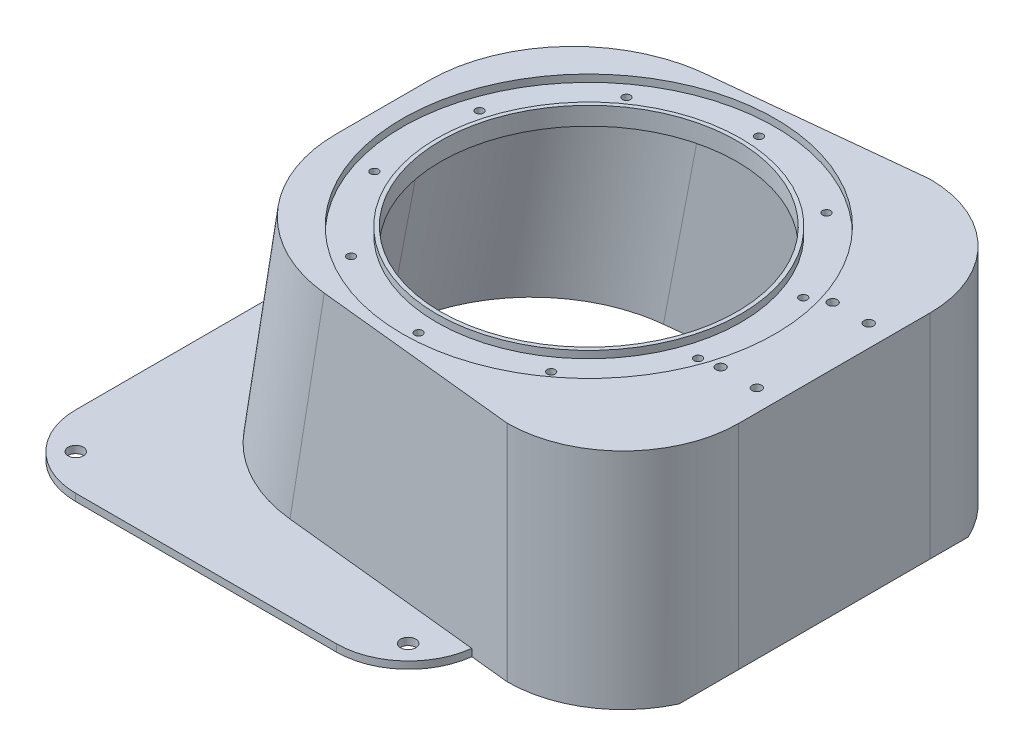
SolidWorks part; units mm, degrees
ref_plane "정면" through (0, 0, 0) normal (0, 0, 1) x (1, 0, 0)
ref_plane "윗면" through (0, 0, 0) normal (0, 1, 0) x (1, 0, 0)
ref_plane "우측면" through (0, 0, 0) normal (1, 0, 0) x (0, 0, -1)
sketch "스케치1" plane through (0, 0, 0) normal (0, 1, 0) x (1, 0, 0)
  line L0 (-65, -45) -> (36, -55.5)
  line L1 (-65, 45) -> (65, 45) construction
  line L2 (-65, 45) -> (-65, -45)
  line L3 (-65, -45) -> (65, -45) construction
  line L4 (65, 45) -> (65, -45) construction
  line L5 (-65, 45) -> (65, -45) construction
  line L6 (-65, -45) -> (65, 45) construction
  line L7 (65, 55.5) -> (36, 55.5)
  line L8 (65, 55.5) -> (65, -55.5)
  line L9 (65, -55.5) -> (36, -55.5)
  line L10 (36, 55.5) -> (36, -55.5) construction
  line L11 (65, 55.5) -> (36, -55.5) construction
  line L12 (65, -55.5) -> (36, 55.5) construction
  line L13 (-65, 45) -> (36, 55.5)
  line L20 (-68, -47.7043) -> (35.8445, -58.5)
  line L21 (68, -58.5) -> (35.8445, -58.5)
  line L22 (68, 58.5) -> (68, -58.5)
  line L23 (68, 58.5) -> (35.8445, 58.5)
  line L24 (-68, 47.7043) -> (35.8445, 58.5)
  line L25 (-68, 47.7043) -> (-68, -47.7043)
  point P0 (0, 0)
  point P9 (50.5, 0)
  dimension "D1" = 90
  dimension "D2" = 111
  dimension "D3" = 10.5
  dimension "D4" = 10.5
  dimension "D5" = 29
  dimension "D7" = 136
  dimension "D6" = 3
extrude "보스-돌출1" add sketch "스케치1" along normal blind 60
sketch "스케치2" plane through (0, 60, 0) normal (0, 1, 0) x (1, 0, 0)
  line L4 (-68, 47.7043) -> (35.8445, 58.5)
  line L10 (35.8445, 58.5) -> (68, 58.5)
  line L11 (68, 58.5) -> (68, -58.5)
  line L12 (68, -58.5) -> (35.8445, -58.5)
  line L14 (35.8445, -58.5) -> (-68, -47.7043)
  line L15 (-68, -47.7043) -> (-68, 47.7043)
  point P2 (0, 0)
extrude "보스-돌출2" add sketch "스케치2" along normal blind 2
sketch "스케치3" plane through (0, 60, 0) normal (0, -1, 0) x (1, 0, 0)
  circle A2 centre (0, 0) radius 53
  dimension "D1" = 106
extrude "보스-돌출3" add sketch "스케치3" along normal blind 3
sketch "스케치4" plane through (0, 62, 0) normal (0, 1, 0) x (1, 0, 0)
  circle A0 centre (0, 0) radius 51.6
  dimension "D1" = 103.2
extrude "컷-돌출1" cut sketch "스케치4" against normal blind 2
sketch "스케치5" plane through (0, 60, 0) normal (0, 1, 0) x (1, 0, 0)
  circle A0 centre (0, 0) radius 41
  dimension "D1" = 82
extrude "컷-돌출2" cut sketch "스케치5" against normal through all
sketch "스케치6" plane through (0, 60, 0) normal (0, 1, 0) x (1, 0, 0)
  circle A0 centre (0, 0) radius 42.1
  circle A1 centre (0, 0) radius 41
  circle A2 centre (0, 0) radius 41 construction
  dimension "D1" = 84.2
extrude "보스-돌출4" add sketch "스케치6" along normal blind 2
sketch "스케치9" plane through (0, 60, 0) normal (0, -1, 0) x (1, 0, 0)
  line L0 (65, 55.5) -> (65, -55.5) construction
  line L1 (41, -23.5) -> (65, -23.5)
  line L2 (41, -23.5) -> (41, 23.5)
  line L3 (41, 23.5) -> (65, 23.5)
  line L4 (65, -23.5) -> (65, 23.5)
  line L5 (41, -23.5) -> (65, 23.5) construction
  line L6 (41, 23.5) -> (65, -23.5) construction
  circle A0 centre (0, 0) radius 53 construction
  point P0 (53, 0)
  dimension "D1" = 47
extrude "보스-돌출6" add sketch "스케치9" along normal blind 9
sketch "스케치10" plane through (0, 51, 0) normal (0, -1, 0) x (1, 0, 0)
  line L0 (65, 55.5) -> (65, -55.5) construction
  line L1 (41, -18.5) -> (65, -18.5)
  line L2 (41, -18.5) -> (41, 18.5)
  line L3 (41, 18.5) -> (65, 18.5)
  line L4 (65, -18.5) -> (65, 18.5)
  line L5 (41, -18.5) -> (65, 18.5) construction
  line L6 (41, 18.5) -> (65, -18.5) construction
  line L7 (41, 0) -> (41, 23.5) construction
  line L8 (41, -23.5) -> (65, -23.5) construction
  point P0 (53, 0)
  dimension "D1" = 37
  dimension "D2" = 5
extrude "컷-돌출6" cut sketch "스케치10" against normal blind 6
sketch "스케치7" plane through (0, 60, 0) normal (0, 1, 0) x (1, 0, 0)
  circle A0 centre (0, 0) radius 47.1 construction
  circle A1 centre (0, 0) radius 51.6 construction
  circle A2 centre (0, 47.1) radius 1.1
  circle A3 centre (27.6847, 38.1047) radius 1.1
  circle A4 centre (44.7948, 14.5547) radius 1.1
  circle A5 centre (44.7948, -14.5547) radius 1.1
  circle A6 centre (27.6847, -38.1047) radius 1.1
  circle A7 centre (0, -47.1) radius 1.1
  circle A8 centre (-27.6847, -38.1047) radius 1.1
  circle A9 centre (-44.7948, -14.5547) radius 1.1
  circle A10 centre (-44.7948, 14.5547) radius 1.1
  circle A11 centre (-27.6847, 38.1047) radius 1.1
  point P27 (0, 0)
  dimension "D1" = 4.5
  dimension "D2" = 2.2
  dimension "D3" = 10
extrude "컷-돌출3" cut sketch "스케치7" against normal through all
sketch "스케치11" plane through (0, 57, 0) normal (0, -1, 0) x (1, 0, 0)
  line L0 (65, -18.5) -> (65, 18.5) construction
  line L1 (52, 15.5) -> (62, 15.5) construction
  line L2 (52, 15.5) -> (52, -15.5) construction
  line L3 (52, -15.5) -> (62, -15.5) construction
  line L4 (62, 15.5) -> (62, -15.5) construction
  line L5 (65, 18.5) -> (41, 18.5) construction
  line L6 (41, -18.5) -> (65, -18.5) construction
  circle A1 centre (52, 15.5) radius 1.3
  circle A2 centre (52, -15.5) radius 1.3
  circle A3 centre (62, 15.5) radius 1.3
  circle A4 centre (62, -15.5) radius 1.3
  dimension "D5" = 2.6
  dimension "D1" = 3
  dimension "D2" = 3
  dimension "D3" = 3
  dimension "D4" = 10
  dimension "D6" = 31
extrude "컷-돌출7" cut sketch "스케치11" against normal up to next
fillet "필렛2" radius 4.5 4 edges at (53, 51, 23.5) (53, 51, -23.5) (56.2526, 60, -23.5) (56.2526, 60, 23.5)
chamfer "모따기1" distance 62 angle 10 2 edges at (-68, 62, 0) (-65, 60, 0) first distance on face at (-68, 31, 0) first distance on face at (-65, 30, 0)
fillet "필렛3" radius 40 4 edges at (-59.3575, 30, 45.5866) (-59.3575, 30, -45.5866) (-62.5339, 31, -48.2725) (-62.5339, 31, 48.2725)
fillet "필렛4" radius 32 4 edges at (65, 30, -55.5) (65, 30, 55.5) (68, 31, -58.5) (68, 31, 58.5)
chamfer "모따기3" distance 3 angle 45 1 edges at (68, 0, 0) tangent propagation no
sketch "스케치12" plane through (0, 0, 0) normal (0, -1, 0) x (1, 0, 0)
  line L0 (65, -18.5) -> (65, 18.5) construction
  line L1 (-87, 75) -> (25, 75)
  line L2 (-87, 75) -> (-87, -75)
  line L3 (-87, -75) -> (25, -75)
  line L4 (25, 75) -> (25, 54.3564)
  line L5 (-87, 75) -> (25, -75) construction
  line L6 (-87, -75) -> (25, 75) construction
  line L16 (25, -54.3564) -> (25, -75)
  line L19 (36.1547, -55.5161) -> (-31.2089, -48.5129)
  line L20 (-65, -11.584) -> (-65, 11.584)
  line L21 (-31.2089, 48.5129) -> (36.1547, 55.5161)
  line L22 (25, -54.3564) -> (-31.2089, -48.5129)
  line L23 (-65, -11.584) -> (-65, 11.584)
  line L24 (-31.2089, 48.5129) -> (25, 54.3564)
  spline S0 degree 3 poles (-4324.0812, 2425.2241) (343.868, 408.1956) (74.8433, -80.1677) (-40.1959, -46.5353) (-42.3472, -45.6886) (-46.4571, -43.6234) (-48.4156, -42.4051) (-52.074, -39.6383) (-53.7739, -38.0899) (-56.8582, -34.7154) (-58.2425, -32.8895) (-60.6496, -29.0218) (-61.6724, -26.98) (-63.3225, -22.7493) (-63.9498, -20.5604) (-85.9526, 96.2197) (443.3445, 308.5028) (1988.1513, -4518.7728) knots -6.252758 -6.252758 -6.252758 -6.252758 0.125 0.125 0.25 0.25 0.375 0.375 0.5 0.5 0.625 0.625 0.75 0.75 0.875 0.875 7.30812 7.30812 7.30812 7.30812 only from (-31.2089, -48.5129) to (-65, -11.584)
  spline S1 degree 3 poles (1988.1715, 4518.836) (443.3491, -308.5047) (-85.9527, -96.2202) (-63.9498, 20.5604) (-63.3225, 22.7493) (-61.6724, 26.98) (-60.6496, 29.0218) (-58.2425, 32.8895) (-56.8582, 34.7154) (-53.7739, 38.0899) (-52.074, 39.6383) (-48.4156, 42.4051) (-46.4571, 43.6234) (-42.3472, 45.6886) (-40.1959, 46.5353) (74.8434, 80.1678) (343.8687, -408.1968) (-4324.0988, -2425.2317) knots -6.308148 -6.308148 -6.308148 -6.308148 0.125 0.125 0.25 0.25 0.375 0.375 0.5 0.5 0.625 0.625 0.75 0.75 0.875 0.875 7.252766 7.252766 7.252766 7.252766 only from (-65, 11.584) to (-31.2089, 48.5129)
  spline S2 degree 3 poles (-31.2089, -48.5129) (-33.5019, -48.2746) (-35.7732, -47.8283) (-40.1959, -46.5353) (-42.3472, -45.6886) (-46.4571, -43.6234) (-48.4156, -42.4051) (-52.074, -39.6383) (-53.7739, -38.0899) (-56.8582, -34.7154) (-58.2425, -32.8895) (-60.6496, -29.0218) (-61.6724, -26.98) (-63.3225, -22.7493) (-63.9498, -20.5604) (-64.7886, -16.1087) (-65, -13.8459) (-65, -11.584) knots 0 0 0 0 0.125 0.125 0.25 0.25 0.375 0.375 0.5 0.5 0.625 0.625 0.75 0.75 0.875 0.875 1 1 1 1
  spline S3 degree 3 poles (-65, 11.584) (-65, 13.8459) (-64.7886, 16.1087) (-63.9498, 20.5604) (-63.3225, 22.7493) (-61.6724, 26.98) (-60.6496, 29.0218) (-58.2425, 32.8895) (-56.8582, 34.7154) (-53.7739, 38.0899) (-52.074, 39.6383) (-48.4156, 42.4051) (-46.4571, 43.6234) (-42.3472, 45.6886) (-40.1959, 46.5353) (-35.7732, 47.8283) (-33.5019, 48.2746) (-31.2089, 48.5129) knots 0 0 0 0 0.125 0.125 0.25 0.25 0.375 0.375 0.5 0.5 0.625 0.625 0.75 0.75 0.875 0.875 1 1 1 1
  point P4 (-31, 0)
  point P7 (0, 0)
  dimension "D2" = 112
  dimension "D1" = 40
  dimension "D3" = 150
  dimension "D4" = 3
extrude "보스-돌출7" add sketch "스케치12" against normal blind 2
fillet "필렛6" radius 20 4 edges at (25, 1, 75) (-87, 1, 75) (25, 1, -75) (-87, 1, -75)
sketch "스케치13" plane through (0, 0, 0) normal (0, -1, 0) x (1, 0, 0)
  line L1 (-77, 65) -> (15, 65) construction
  line L2 (-77, 65) -> (-77, -65) construction
  line L3 (-77, -65) -> (15, -65) construction
  line L4 (15, 65) -> (15, -65) construction
  line L5 (-77, 65) -> (15, -65) construction
  line L6 (-77, -65) -> (15, 65) construction
  line L8 (65, -18.5) -> (65, 18.5) construction
  circle A0 centre (-77, 65) radius 2.1
  circle A1 centre (15, 65) radius 2.1
  circle A2 centre (-75.4995, -65) radius 2.1
  circle A3 centre (15, -65) radius 2.1
  point P4 (-31, 0)
  dimension "D4" = 4.2
  dimension "D1" = 92
  dimension "D2" = 130
  dimension "D3" = 50
extrude "컷-돌출8" cut sketch "스케치13" against normal through all
